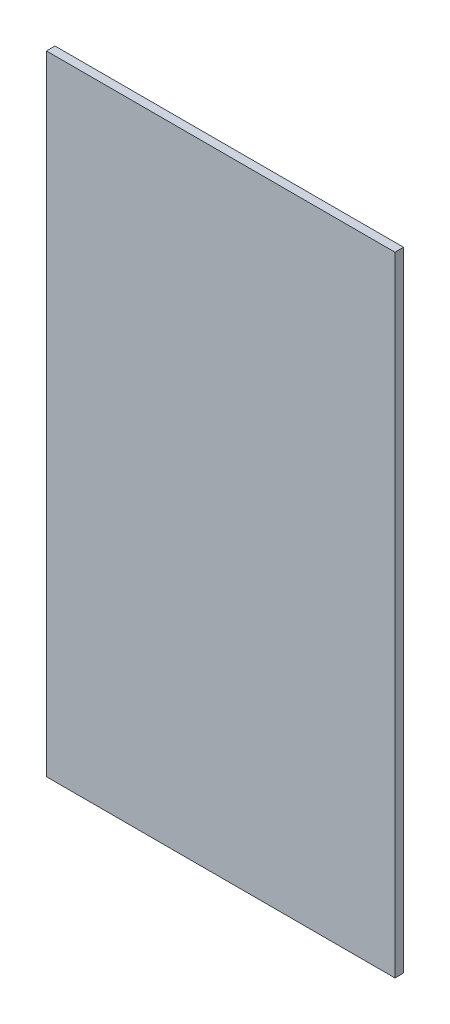
SolidWorks part; units mm, degrees
material "PMMA"
ref_plane "Front Plane" through (0, 0, 0) normal (0, 0, 1) x (1, 0, 0)
ref_plane "Top Plane" through (0, 0, 0) normal (0, 1, 0) x (1, 0, 0)
ref_plane "Right Plane" through (0, 0, 0) normal (1, 0, 0) x (0, 0, -1)
sketch "Sketch1" plane through (0, 0, 0) normal (0, 0, 1) x (1, 0, 0)
  line L1 (-61, -110) -> (61, -110)
  line L2 (-61, -110) -> (-61, 110)
  line L3 (-61, 110) -> (61, 110)
  line L4 (61, -110) -> (61, 110)
  line L5 (-61, -110) -> (61, 110) construction
  line L6 (-61, 110) -> (61, -110) construction
  point P0 (0, 0)
  dimension "D1" = 122
  dimension "D2" = 220
extrude "Boss-Extrude1" add sketch "Sketch1" along normal blind 3
sketch "Sketch2" plane through (0, 0, 0) normal (0, 0, -1) x (-1, 0, 0)
  line L0 (61, 145) -> (61, -145) construction
  line L1 (-61, 314.7216) -> (-204.3993, 314.7216)
  line L2 (-61, 314.7216) -> (-61, -251.9618)
  line L3 (-61, -251.9618) -> (-204.3993, -251.9618)
  line L4 (-204.3993, 314.7216) -> (-204.3993, -251.9618)
  line L6 (61, 279.3211) -> (244.4765, 279.3211)
  line L7 (61, 279.3211) -> (61, -295.1839)
  line L8 (61, -295.1839) -> (244.4765, -295.1839)
  line L9 (244.4765, 279.3211) -> (244.4765, -295.1839)
  line L10 (-61, -145) -> (-61, 145) construction
  dimension "D1" = 122
extrude "Cut-Extrude1" [suppressed] cut sketch "Sketch2" against normal through all
sketch "Sketch3" [suppressed] plane through (49, 0, 0) normal (1, 0, 0) x (0, 0, -1)
  circle A0 centre (-6.722, 55.3681) radius 5.3835
surface "Surface-Extrude1" [suppressed] sketch "Sketch3"
sketch "Sketch4" [suppressed] plane through (-49, 0, 0) normal (-1, 0, 0) x (0, 0, 1)
  line L1 (2, 80) -> (0, 80) construction
  line L2 (0, -80) -> (0, 80) construction
  point P0 (7.5, 76)
  dimension "D1" = 4
  dimension "D2" = 7.5
ref_axis "Axis1" [suppressed] through (-49, 76, 7.5) along (1, 0, 0)
sketch "Sketch5" [suppressed] plane through (0, 0, 0) normal (0, 0, -1) x (-1, 0, 0)
  line L0 (49, 80) -> (49, -80) construction
  line L1 (-49, 80) -> (49, 80)
  line L2 (-49, 80) -> (-49, 60.2594)
  line L3 (-49, 60.2594) -> (49, 60.2594)
  line L4 (49, 80) -> (49, 60.2594)
extrude "Cut-Extrude2" [suppressed] cut sketch "Sketch5" against normal blind 3
sketch "Sketch6" [suppressed] plane through (0, 0, 2) normal (0, 0, 1) x (1, 0, 0)
  line L0 (0, 0) -> (103.2002, 0) construction
  line L1 (-40, 80) -> (-40, 108.3319) construction
  line L2 (-40, 80) -> (-27.987, 80) construction
  line L3 (0, 0) -> (0, 138.3235) construction
  line L4 (40, 80) -> (27.987, 80) construction
  line L5 (40, 80) -> (40, 108.3319) construction
  line L6 (40, -80) -> (40, -108.3319) construction
  line L7 (40, -80) -> (27.987, -80) construction
  line L8 (-40, -80) -> (-27.987, -80) construction
  line L9 (-40, -80) -> (-40, -108.3319) construction
  circle A0 centre (-40, 80) radius 4.5
  circle A2 centre (-45.8, 85.8) radius 1.95
  circle A3 centre (-45.8, 74.2) radius 1.95
  circle A4 centre (-34.2, 74.2) radius 1.95
  circle A5 centre (-34.2, 85.8) radius 1.95
  circle A6 centre (34.2, 85.8) radius 1.95
  circle A7 centre (34.2, 74.2) radius 1.95
  circle A8 centre (45.8, 74.2) radius 1.95
  circle A9 centre (45.8, 85.8) radius 1.95
  circle A10 centre (40, 80) radius 4.5
  circle A11 centre (40, -80) radius 4.5
  circle A12 centre (45.8, -85.8) radius 1.95
  circle A13 centre (45.8, -74.2) radius 1.95
  circle A14 centre (34.2, -74.2) radius 1.95
  circle A15 centre (34.2, -85.8) radius 1.95
  circle A16 centre (-34.2, -85.8) radius 1.95
  circle A17 centre (-34.2, -74.2) radius 1.95
  circle A18 centre (-45.8, -74.2) radius 1.95
  circle A19 centre (-45.8, -85.8) radius 1.95
  circle A20 centre (-40, -80) radius 4.5
  circle A21 centre (-40, 80) radius 5.1 construction
  dimension "D1" = 9
  dimension "D3" = 3.9
extrude "Leandut_holes" [suppressed] cut sketch "Sketch6" against normal through all
chamfer "Chamfer1" [suppressed] distance 5 angle 45
sketch "Sketch7" [suppressed] plane through (0, 0, 2) normal (0, 0, 1) x (1, 0, 0)
  line L0 (106, 145) -> (-106, 145) construction
  line L1 (-56, -125) -> (56, -125)
  line L2 (-56, -125) -> (-56, 125)
  line L3 (-56, 125) -> (56, 125)
  line L4 (56, -125) -> (56, 125)
  line L5 (-56, -125) -> (56, 125) construction
  line L6 (-56, 125) -> (56, -125) construction
  line L7 (-106, 145) -> (-106, -145) construction
  point P0 (0, 0)
  dimension "D1" = 20
  dimension "D2" = 50
  dimension "D3" = 112
extrude "Plunger-Window" [suppressed] cut sketch "Sketch7" against normal through all
sketch "Sketch8" [suppressed] plane through (0, 0, 2) normal (0, 0, 1) x (1, 0, 0)
  line L0 (106, 145) -> (56, 145) construction
  line L1 (-56, 125) -> (56, 125)
  line L2 (-56, 125) -> (-56, 145)
  line L3 (-56, 145) -> (56, 145)
  line L4 (56, 125) -> (56, 145)
  line L5 (56, -125) -> (56, 125) construction
extrude "Cut-Extrude3" [suppressed] cut sketch "Sketch8" against normal blind 5
